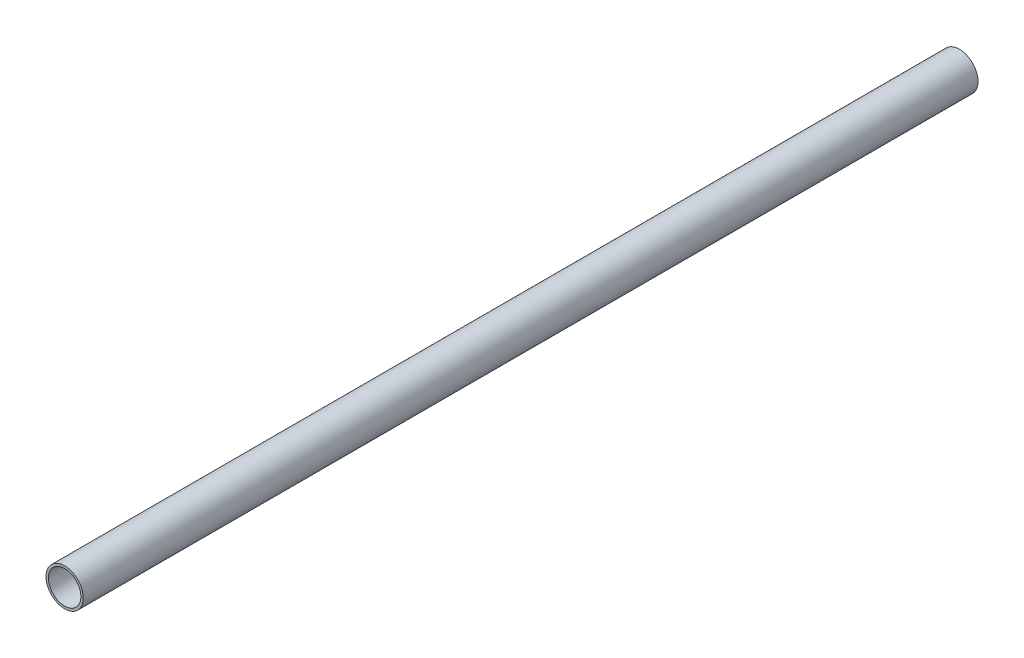
SolidWorks part; units mm, degrees
material "6061 Alloy"
ref_plane "Front Plane" through (0, 0, 0) normal (0, 0, 1) x (1, 0, 0)
ref_plane "Top Plane" through (0, 0, 0) normal (0, 1, 0) x (1, 0, 0)
ref_plane "Right Plane" through (0, 0, 0) normal (1, 0, 0) x (0, 0, -1)
sketch "Sketch1" plane through (0, 0, 0) normal (0, 0, 1) x (1, 0, 0)
  line L0 (-6.35, 0) -> (6.35, 0) construction
  line L1 (0, 0) -> (0, 1.0456) construction
  point P0 (-5.5372, 0)
  point P4 (0, 0)
  point P6 (5.5372, 0)
  dimension "OD" = 12.7
  dimension "ID" = 11.0744
sketch "Sketch2" plane through (0, 0, 0) normal (0, 0, 1) x (1, 0, 0)
  line L0 (-6.35, 0) -> (6.35, 0) construction
  circle A0 centre (0, 0) radius 5.5372
  circle A1 centre (0, 0) radius 6.35
  dimension "D1" = 11.0744
  dimension "D2" = 12.7
extrude "Boss-Extrude1" add sketch "Sketch2" along normal mid plane 304.8
sketch "Sketch3" plane through (0, 0, 0) normal (1, 0, 0) x (0, 0, -1)
  line L0 (152.4, 0) -> (-152.4, 0) construction
  line L1 (-152.4, 6.35) -> (-152.4, -6.35) construction
  line L2 (0, 0) -> (0, 21.8825) construction
  point P0 (-150.876, 0)
  point P6 (0, 0)
  point P8 (150.876, 0)
  dimension "D1" = 301.752
ref_axis "Center Axis 1" through (0, 0, 152.4) along (0, 0, -1)
ref_plane "Contact Plane 1" through (0, 0, 152.4) normal (0, 0, 1) x (1, 0, 0)
ref_plane "Contact Plane 2" through (0, 0, -152.4) normal (0, 0, -1) x (-1, 0, 0)
equation "\"D1@Sketch2\"=\"ID@Sketch1\""
equation "\"D2@Sketch2\"=\"OD@Sketch1\""
equation "\"D1@Sketch3\"=\"Length@Boss-Extrude1\"*0.99"
